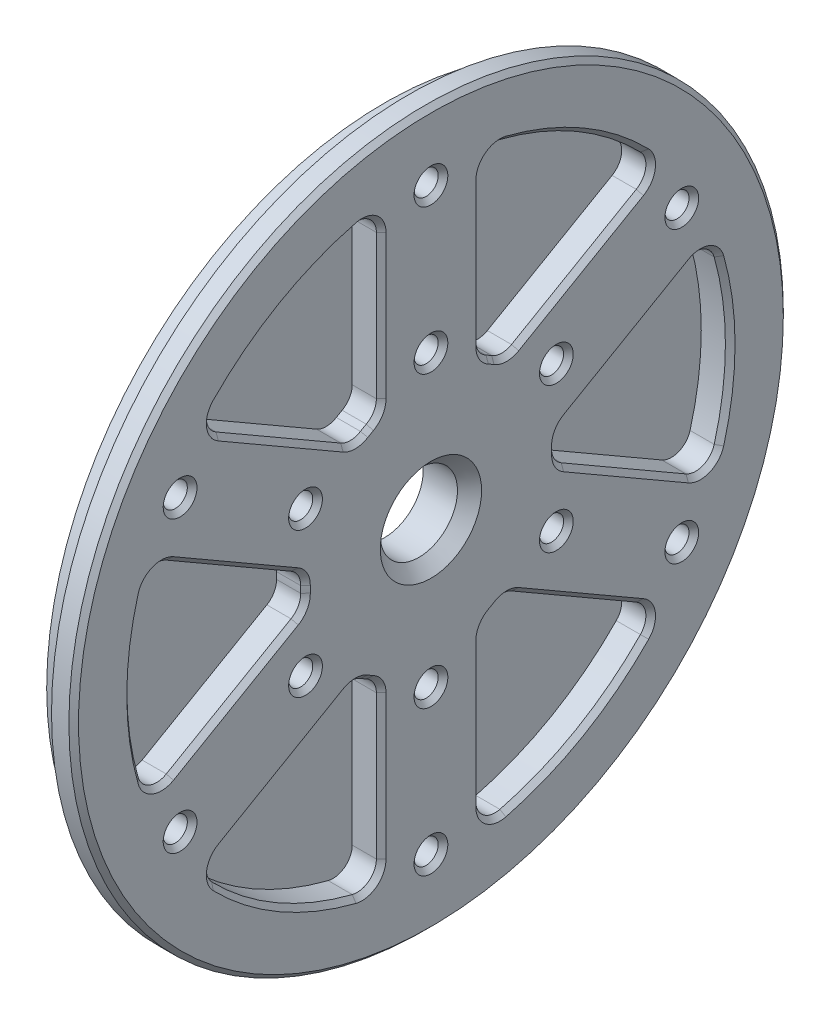
SolidWorks part; units mm, degrees
ref_plane "Front Plane" through (0, 0, 0) normal (0, 0, 1) x (1, 0, 0)
ref_plane "Top Plane" through (0, 0, 0) normal (0, 1, 0) x (1, 0, 0)
ref_plane "Right Plane" through (0, 0, 0) normal (1, 0, 0) x (0, 0, -1)
sketch "Sketch1" plane through (0, 0, 0) normal (1, 0, 0) x (0, 0, -1)
  circle A0 centre (0, 0) radius 37
  dimension "D1" = 74
extrude "Boss-Extrude1" add sketch "Sketch1" along normal mid plane 2.8
sketch "Sketch2" plane through (1.4, 0, 0) normal (1, 0, 0) x (0, 0, -1)
  line L0 (0, 0) -> (0, 30) construction
  circle A0 centre (0, 0) radius 30 construction
  circle A1 centre (0, 30) radius 1.25
  dimension "D1" = 60
  dimension "D2" = 2.5
extrude "Cut-Extrude1" cut sketch "Sketch2" against normal blind 3
chamfer "Chamfer1" distance 0.5 angle 45 1 edges at (1.4, 30, -1.25)
pattern_circular "CirPattern1" count 6 over 360 about axis through (1.4, 0, 0) along (-1, 0, 0) of "Cut-Extrude1", "Chamfer1"
chamfer "Chamfer2" distance 0.5 angle 45 1 edges at (1.4, 0, -37)
sketch "Sketch3" plane through (1.4, 0, 0) normal (1, 0, 0) x (0, 0, -1)
  line L0 (0, 0) -> (0, 15) construction
  circle A0 centre (0, 0) radius 15 construction
  circle A1 centre (0, 15) radius 1.25
  dimension "D1" = 30
  dimension "D2" = 2.5
extrude "Cut-Extrude2" cut sketch "Sketch3" against normal blind 3
chamfer "Chamfer3" distance 0.5 angle 45 1 edges at (1.4, 15, -1.25)
pattern_circular "CirPattern2" count 6 over 360 about axis through (1.4, 0, 0) along (-1, 0, 0) of "Chamfer3", "Cut-Extrude2"
sketch "Sketch4" plane through (1.4, 0, 0) normal (1, 0, 0) x (0, 0, -1)
  circle A0 centre (0, 0) radius 4
  dimension "D1" = 8
extrude "Cut-Extrude3" cut sketch "Sketch4" against normal up to surface (2.8 mm away) up to face at (-1.4, 8.5825, 12.3654)
chamfer "Chamfer4" distance 1.25 angle 45 1 edges at (1.4, 0, -4)
sketch "Sketch5" plane through (-1.4, 0, 0) normal (-1, 0, 0) x (0, 0, 1)
  circle A0 centre (0, 0) radius 35
  circle A1 centre (0, 0) radius 37 construction
  circle A2 centre (0, 0) radius 4 construction
  circle A3 centre (0, 0) radius 4
  dimension "D1" = 2
extrude "Boss-Extrude2" add sketch "Sketch5" along normal blind 2
sketch "Sketch6" plane through (-1.4, 0, 0) normal (-1, 0, 0) x (0, 0, 1)
  circle A0 centre (0, 0) radius 35 construction
  circle A1 centre (0, 0) radius 37
  circle A2 centre (0, 0) radius 37
  circle A3 centre (0, 0) radius 35
  dimension "D1" = 0
extrude "Cut-Extrude4" cut sketch "Sketch6" against normal blind 0.5
sketch "Sketch7" plane through (1.4, 0, 0) normal (1, 0, 0) x (0, 0, -1)
  line L0 (0, 0) -> (-6.5, 11.2583) construction
  line L1 (-6.5, 11.2583) -> (-7.5, 12.9904) construction
  circle A3 centre (0, 0) radius 36.5 construction
  arc A4 (-12.9904, 7.5) -> (0, 15) centre (0, 0) cw construction
  circle A5 centre (0, 15) radius 1.25 construction
  line B0 (-5.1506, 13.1859) -> (-5.1506, 28.1046)
  line B1 (-21.764, 18.5129) -> (-8.844, 11.0535)
  arc B2 (-5.1506, 28.1046) -> (-7.6438, 30.0428) centre (-7.1506, 28.1046) ccw
  arc B3 (-6.1972, 11.4278) -> (-5.1506, 13.1859) centre (-7.1506, 13.1859) ccw
  arc B4 (-6.1972, 11.4278) -> (-6.7982, 11.0808) centre (0, 0) ccw
  arc B5 (-8.844, 11.0535) -> (-6.7982, 11.0808) centre (-7.844, 12.7856) ccw
  arc B6 (-22.196, 21.6411) -> (-21.764, 18.5129) centre (-20.764, 20.2449) ccw
  arc B7 (-7.6438, 30.0428) -> (-22.196, 21.6411) centre (0, 0) ccw
sketch_block_instance "Block-BLOCK 1 - MOTOR 6 - ROBOT DOG-3"
sketch_block "Block-BLOCK 1 - MOTOR 6 - ROBOT DOG"
extrude "Cut-Extrude5" cut sketch "Sketch7" against normal blind 3
chamfer "Chamfer5" distance 0.5 angle 45 8 edges at (1.4, 20.6453, 5.1506) (1.4, 29.6836, 5.9231) (1.4, 12.1629, 5.4321) (1.4, 26.8468, 15.5) (1.4, 11.2583, 6.5) (1.4, 19.9713, 22.7452) (1.4, 10.7858, 7.8173) (1.4, 14.7832, 15.304)
pattern_circular "CirPattern3" count 6 over 360 about axis through (1.4, 0, 0) along (-1, 0, 0) of "Cut-Extrude5", "Chamfer5"
extrude "Cut-Extrude6" cut sketch "Sketch2<2>" against normal blind 3
sketch "Sketch2<2>" plane through (1.4, 0, 0) normal (1, 0, 0) x (0, 0, -1) same geometry as "Sketch2"
pattern_circular "CirPattern4" count 6 over 360 about axis through (1.4, 0, 0) along (-1, 0, 0) of "Cut-Extrude6"
